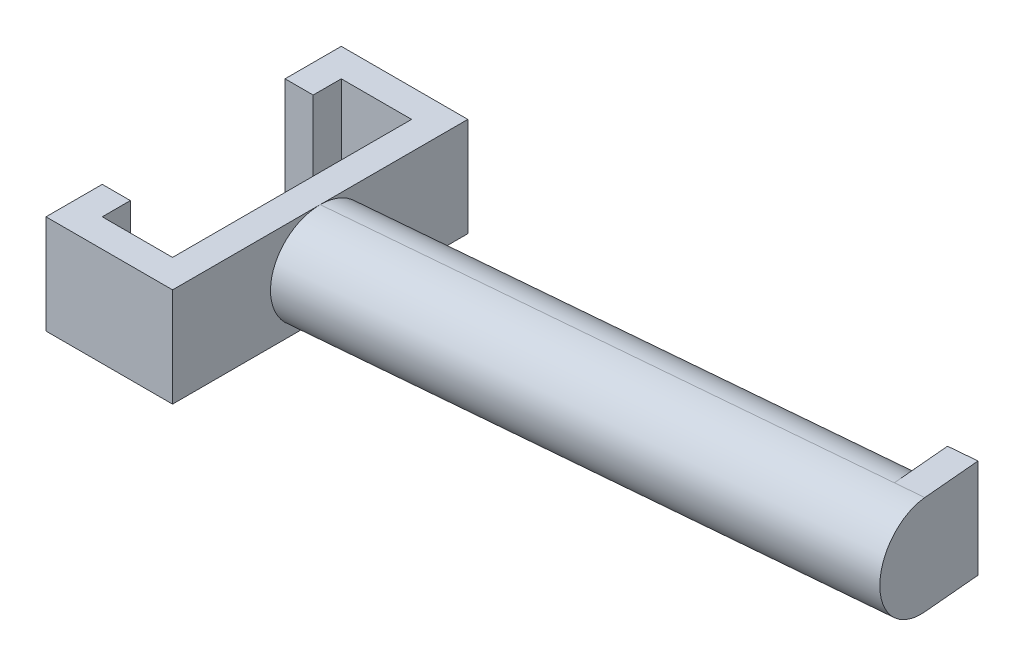
SolidWorks part; units mm, degrees
ref_plane "Front Plane" through (0, 0, 0) normal (0, 0, 1) x (1, 0, 0)
ref_plane "Top Plane" through (0, 0, 0) normal (0, 1, 0) x (1, 0, 0)
ref_plane "Right Plane" through (0, 0, 0) normal (1, 0, 0) x (0, 0, -1)
sketch "Sketch1" plane through (0, 0, 0) normal (0, 1, 0) x (1, 0, 0)
  line L0 (0, 0) -> (7.1437, 0)
  line L1 (7.1437, 0) -> (7.1438, 5.5297)
  line L2 (7.1438, 5.5297) -> (38.7729, 8.2969)
  line L3 (38.7729, 8.2969) -> (38.2859, 13.8636)
  line L4 (38.2859, 13.8636) -> (7.1437, 11.139)
  line L5 (7.1437, 11.139) -> (7.1437, 16.6687)
  line L6 (7.1437, 16.6687) -> (0, 16.6687)
  line L8 (1.5875, 15.0812) -> (5.5562, 15.0812)
  line L9 (5.5562, 15.0812) -> (5.5563, 1.5875)
  line L10 (5.5563, 1.5875) -> (1.5875, 1.5875)
  line L12 (0, 16.6687) -> (0, 13.4937)
  line L13 (0, 13.4937) -> (1.5875, 13.4937)
  line L14 (1.5875, 13.4937) -> (1.5875, 15.0812)
  line L15 (0, 0) -> (0, 3.175)
  line L16 (0, 3.175) -> (1.5875, 3.175)
  line L17 (1.5875, 3.175) -> (1.5875, 1.5875)
  dimension "D1" = 1.5875
  dimension "D2" = 1.5875
  dimension "D3" = 1.5875
  dimension "D4" = 13.4937
  dimension "D5" = 5.588
  dimension "D6" = 85
  dimension "D7" = 31.75
  dimension "D8" = 3.9688
extrude "Boss-Extrude1" add sketch "Sketch1" along normal blind 5.588
fillet "Fillet1" radius 2.794 4 edges at (22.9583, 0, -6.9133) (22.7148, 0, -12.5013) (22.9583, 5.588, -6.9133) (22.7148, 5.588, -12.5013)
sketch "Sketch2" plane through (39.1988, 0, -3.4294) normal (0.9962, 0, -0.0872) x (-0.0872, 0, -0.9962)
  line L0 (7.68, 5.588) -> (10.982, 5.588)
  line L1 (7.68, 5.588) -> (15.9827, 5.588) construction
  line L2 (10.982, 5.588) -> (10.982, 0)
  line L3 (7.68, 0) -> (15.9827, 0) construction
  line L4 (10.982, 0) -> (7.68, 0)
  arc A0 (7.68, 5.588) -> (7.68, 0) centre (7.68, 2.794) ccw
  arc A1 (4.886, 2.794) -> (7.68, 0) centre (7.68, 2.794) ccw construction
  dimension "D1" = 3.302
extrude "Boss-Extrude2" add sketch "Sketch2" against normal blind 1.5875
